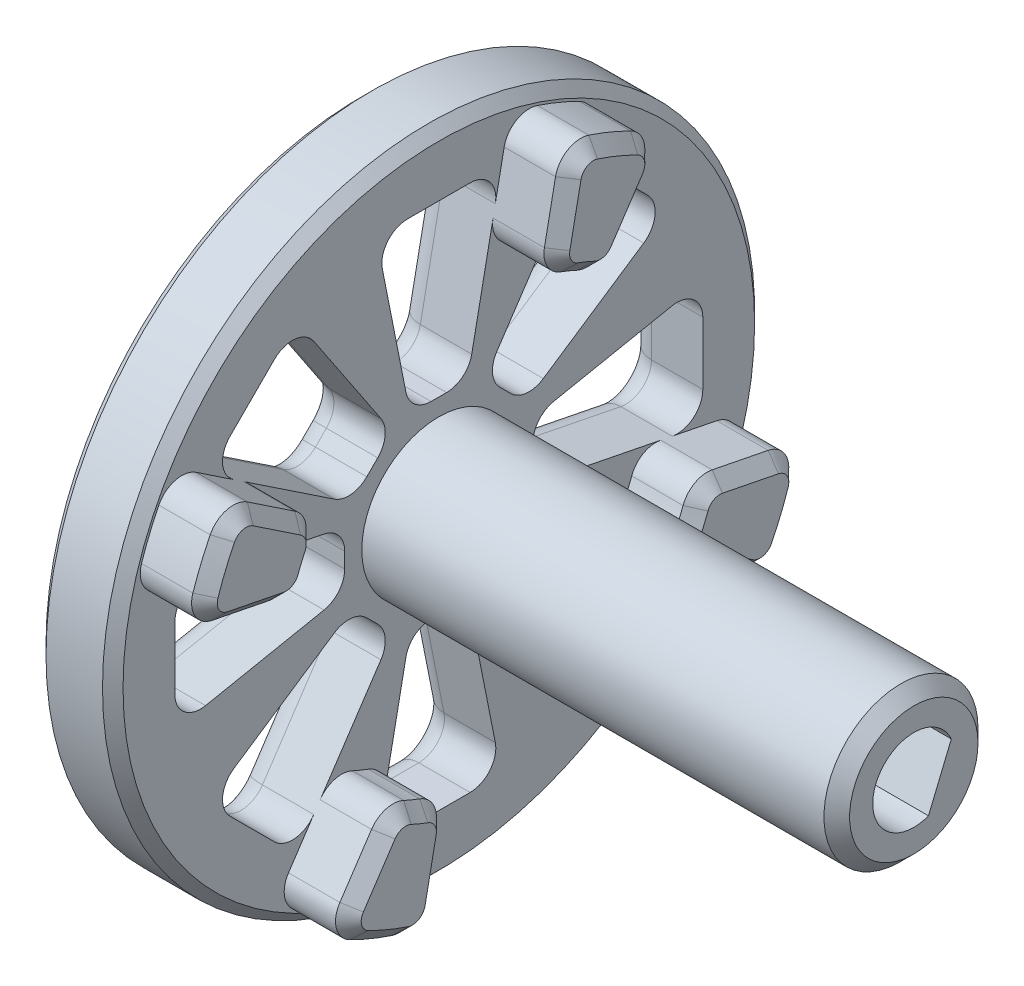
SolidWorks part; units mm, degrees
ref_plane "Спереди" through (0, 0, 0) normal (0, 0, 1) x (1, 0, 0)
ref_plane "Сверху" through (0, 0, 0) normal (0, 1, 0) x (1, 0, 0)
ref_plane "Справа" through (0, 0, 0) normal (1, 0, 0) x (0, 0, -1)
sketch "Sketch2" plane through (0, 0, 0) normal (1, 0, 0) x (0, 0, -1)
  circle A0 centre (0, 0) radius 3
  dimension "D1" = 6
extrude "Boss-Extrude1" add sketch "Sketch2" along normal blind 17.5 and the other way blind 1.5 contours A0
sketch "Sketch1" plane through (17.5, 0, 0) normal (1, 0, 0) x (0, 0, -1)
  line L0 (1.3517, 0.6502) -> (0.496, -1.4156) construction
  line L1 (1.4609, 0.6525) -> (0.5716, -1.4944)
  arc A0 (1.3517, 0.6502) -> (0.496, -1.4156) centre (0, 0) ccw construction
  arc A1 (1.4609, 0.6525) -> (0.5716, -1.4944) centre (0, 0) ccw
  dimension "D1" = 3
  dimension "D3" = 0.1
  dimension "D2" = 1
extrude "Отверстие под вал" cut sketch "Sketch1" against normal blind 10
chamfer "Chamfer1" distance 0.5 angle 45 1 edges at (17.5, 0, -3)
sketch "Sketch4" plane through (-1, 0, 0) normal (-1, 0, 0) x (0, 0, 1)
  circle A0 centre (0, 0) radius 12.7
extrude "Фланец" add sketch "Sketch4" along normal blind 3 contours A0
chamfer "Chamfer2" distance 0.4 angle 45 2 edges at (-1, 0, 12.7) (-4, 0, 12.7)
sketch "Sketch5" plane through (-4, 0, 0) normal (-1, 0, 0) x (0, 0, 1)
  circle A0 centre (0, 0) radius 11
sketch "Sketch6" plane through (-4, 0, 0) normal (-1, 0, 0) x (0, 0, 1)
  line L0 (0, -2.1126) -> (0, 14.8245) construction
  line L1 (-0.3011, 3.6663) -> (0.3011, 3.6663)
  line L2 (-1.2192, 10.2818) -> (1.2192, 10.2818)
  line L3 (2.2, 9.0868) -> (1.2819, 4.4712)
  line L4 (-2.2, 9.0868) -> (-1.2819, 4.4712)
  arc A0 (2.2, 9.0868) -> (1.2192, 10.2818) centre (1.2192, 9.2818) ccw
  arc A1 (1.2819, 4.4712) -> (0.3011, 3.6663) centre (0.3011, 4.6663) cw
  arc A2 (-2.2, 9.0868) -> (-1.2192, 10.2818) centre (-1.2192, 9.2818) cw
  arc A3 (-0.3011, 3.6663) -> (-1.2819, 4.4712) centre (-0.3011, 4.6663) cw
  point P9 (0, 10.2818)
  dimension "D3" = 1
  dimension "D1" = 1
  dimension "D2" = 11.25
extrude "Cut-Extrude6" cut sketch "Sketch6" against normal up to next
pattern_circular "CirPattern1" count 8 over 360 about axis through (-4, 0, 0) along (1, 0, 0) of "Cut-Extrude6" reverse direction yes
sketch "Sketch7" [suppressed] plane through (-2, 0, 0) normal (-1, 0, 0) x (0, 0, 1)
  circle A0 centre (0, 0) radius 1.5907
extrude "Boss-Extrude5" [suppressed] add sketch "Sketch7" along normal blind 1
fillet "Fillet1" radius 1 64 edges at (-4, -0.9355, 3.8933) (-4, 0, 3.6663) (-4, 0.9355, 3.8933) (-4, 1.741, 6.779) (-4, 1.9923, 9.9162) (-4, 0, 10.2818) (-4, -1.9923, 9.9162) (-4, -3.4145, 2.0914) (-4, -2.5924, 2.5924) (-4, -2.0914, 3.4145) (-4, -3.5624, 6.0245) (-4, -5.6031, 8.4206) (-4, -7.2704, 7.2704) (-4, -8.4206, 5.6031) (-4, -3.8933, -0.9355) (-4, -3.6663, 0) (-4, -3.8933, 0.9355) (-4, -6.779, 1.741) (-4, -9.9162, 1.9923) (-4, -10.2818, 0) (-4, -9.9162, -1.9923) (-4, -2.0914, -3.4145) (-4, -2.5924, -2.5924) (-4, -3.4145, -2.0914) (-4, -6.0245, -3.5624) (-4, -8.4206, -5.6031) (-4, -7.2704, -7.2704) (-4, -5.6031, -8.4206) (-4, 0.9355, -3.8933) (-4, 0, -3.6663) (-4, -0.9355, -3.8933) (-4, -1.741, -6.779) (-4, -1.9923, -9.9162) (-4, 0, -10.2818) (-4, 1.9923, -9.9162) (-4, 3.4145, -2.0914) (-4, 2.5924, -2.5924) (-4, 2.0914, -3.4145) (-4, 3.5624, -6.0245) (-4, 5.6031, -8.4206) (-4, 7.2704, -7.2704) (-4, 8.4206, -5.6031) (-4, 9.9162, -1.9923) (-4, 10.2818, 0) (-4, 9.9162, 1.9923) (-4, 6.779, 1.741) (-4, 3.8933, 0.9355) (-4, 3.6663, 0) (-4, 3.8933, -0.9355) (-4, 8.4206, 5.6031) (-4, 7.2704, 7.2704) (-4, 5.6031, 8.4206) (-4, 3.5624, 6.0245) (-4, 2.0914, 3.4145) (-4, 2.5924, 2.5924) (-4, 3.4145, 2.0914) (-4, -1.741, 6.779) (-4, -6.0245, 3.5624) (-4, -6.779, -1.741) (-4, -3.5624, -6.0245) (-4, 1.741, -6.779) (-4, 6.0245, -3.5624) (-4, 6.779, -1.741) (-4, 6.0245, 3.5624)
sketch "Sketch8" plane through (-1, 0, 0) normal (1, 0, 0) x (0, 0, -1)
  line L0 (0, 0) -> (6.1495, 14.8463) construction
  circle A0 centre (4.2095, 10.1627) radius 1
  dimension "D1" = 11
extrude "Boss-Extrude6" [suppressed] add sketch "Sketch8" along normal blind 4
chamfer "Chamfer3" [suppressed] distance 0.5 angle 45
pattern_circular "CirPattern3" [suppressed] count 4 over 360 of bodies 112
sketch "Sketch10" plane through (-1, 0, 0) normal (1, 0, 0) x (0, 0, -1)
  line L0 (0, -0.5511) -> (0, 16.3859) construction
  line L6 (0, 0) -> (6.1734, 14.9039) construction
  line L8 (2.5459, 10.8254) -> (2.1125, 8.6468)
  line L9 (5.8545, 9.4549) -> (4.6204, 7.608)
  arc A5 (5.4715, 10.9042) -> (3.8415, 11.5794) centre (0, 0) ccw
  arc A10 (5.8545, 9.4549) -> (5.4715, 10.9042) centre (5.023, 10.0105) ccw
  arc A11 (3.8415, 11.5794) -> (2.5459, 10.8254) centre (3.5266, 10.6303) ccw
  arc A13 (3.368, 7.2565) -> (2.7496, 7.5126) centre (0, 0) ccw
  arc A14 (4.6204, 7.608) -> (3.368, 7.2565) centre (3.789, 8.1636) cw
  arc A15 (2.1125, 8.6468) -> (2.7496, 7.5126) centre (3.0933, 8.4517) ccw
  point P7 (6.4545, 10.3528)
  point P11 (2.7565, 11.8845)
  dimension "D1" = 1
  dimension "D2" = 1
extrude "Boss-Extrude7" add sketch "Sketch10" along normal blind 2.5
chamfer "Chamfer4" distance 0.5 angle 45 8 edges at (1.5, 10.2659, -5.9898) (1.5, 11.2713, -4.6687) (1.5, 8.5314, -5.2375) (1.5, 11.4946, -3.0236) (1.5, 7.2008, -4.0592) (1.5, 9.7361, -2.3292) (1.5, 7.391, -3.0615) (1.5, 7.962, -2.2214)
pattern_circular "CirPattern4" count 4 over 360 about axis through (-1, 0, 0) along (1, 0, 0) of "Chamfer4", "Boss-Extrude7"
